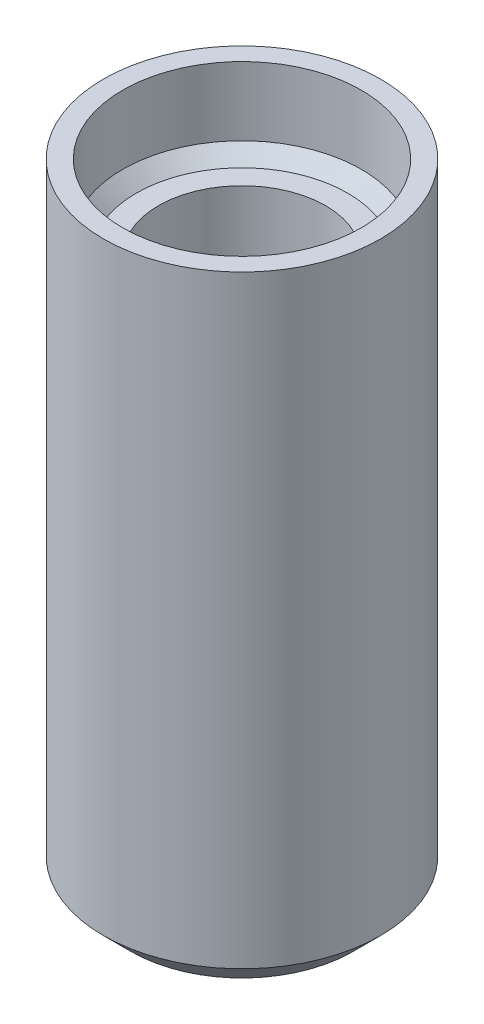
SolidWorks part; units mm, degrees
ref_plane "Front Plane" through (0, 0, 0) normal (0, 0, 1) x (1, 0, 0)
ref_plane "Top Plane" through (0, 0, 0) normal (0, 1, 0) x (1, 0, 0)
ref_plane "Right Plane" through (0, 0, 0) normal (1, 0, 0) x (0, 0, -1)
sketch "Sketch1" plane through (0, 0, 0) normal (0, 1, 0) x (1, 0, 0)
  line L0 (-2.5652, -1.65) -> (2.5652, -1.65)
  circle A0 centre (0, 0) radius 3.05
  circle A1 centre (0, 0) radius 5.05
  dimension "D1" = 6.1
  dimension "D3" = 1.65
  dimension "D2" = 2
extrude "Boss-Extrude1" add sketch "Sketch1" along normal blind 20 contours A1 A0 | L0 A0 region at (0, 0, 2.2227) region at (-4.9072, 0, 0)
sketch "Sketch2" plane through (0, 0, 0) normal (0, -1, 0) x (1, 0, 0)
  circle A1 centre (0, 0) radius 5.05
  circle A2 centre (0, 0) radius 5.05
  dimension "D1" = 0
extrude "Boss-Extrude2" add sketch "Sketch2" against normal blind 2
sketch "Sketch4" plane through (0, 20, 0) normal (0, 1, 0) x (1, 0, 0)
  circle A0 centre (0, 0) radius 4.35
  circle A1 centre (0, 0) radius 5.05
  circle A2 centre (0, 0) radius 5.05
  dimension "D1" = 0
  dimension "D2" = 0.7
extrude "Boss-Extrude3" add sketch "Sketch4" along normal blind 3
chamfer "Chamfer1" distance 1 angle 45 1 edges at (0, 0, 5.05)
chamfer "Chamfer2" distance 0.5 angle 45 1 edges at (0, 20, 4.35)
sketch "Sketch5" plane through (0, 0, 0) normal (0, -1, 0) x (1, 0, 0)
  line L0 (-1.326, 0) -> (1.326, 0) construction
  line L1 (-3.5217, -2) -> (3.5217, -2) construction
  circle A0 centre (0, 0) radius 4.05 construction
  text T0 "<b>5</b>\r\n" font "Calibri" height in points 16
  dimension "D1" = 2
extrude "Cut-Extrude1" cut sketch "Sketch5" against normal blind 0.4
extrude "Boss-Extrude4" add sketch "Sketch5<2>" against normal blind 0.4 separate body
sketch "Sketch5<2>" plane through (0, 0, 0) normal (0, -1, 0) x (1, 0, 0) same geometry as "Sketch5"
equation "\"ID\"= 6.3"
equation "\"notch\"= 6.3 / 2 - 1.5"
equation "\"D3@Sketch1\"=\"notch\""
